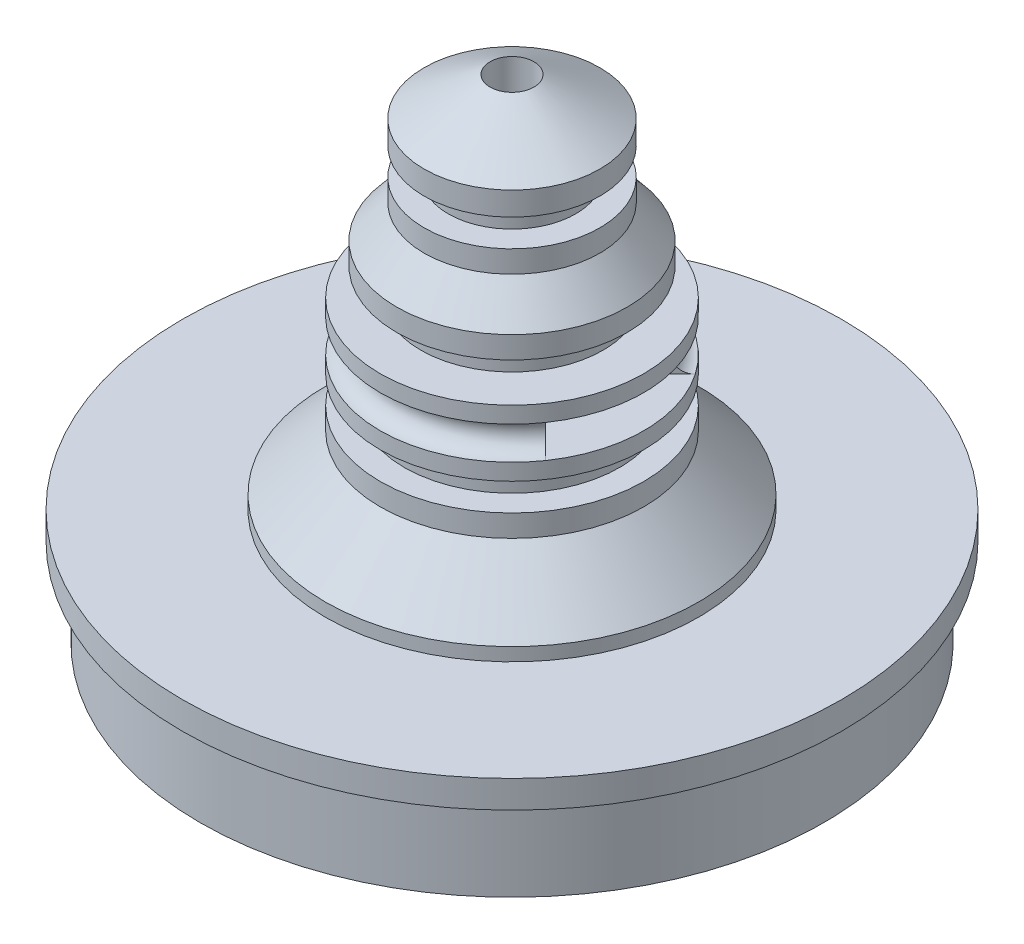
SolidWorks part; units mm, degrees
ref_plane "Спереди" through (0, 0, 0) normal (0, 0, 1) x (1, 0, 0)
ref_plane "Сверху" through (0, 0, 0) normal (0, 1, 0) x (1, 0, 0)
ref_plane "Справа" through (0, 0, 0) normal (1, 0, 0) x (0, 0, -1)
sketch "Эскиз1" plane through (0, 0, 0) normal (0, 0, 1) x (1, 0, 0)
  line L0 (0, 0) -> (0, 60) construction
  line L1 (17, 29) -> (17, 27.8)
  line L2 (2, 62.0979) -> (2, 17.3)
  line L6 (8, 56.5) -> (5.8, 56.5)
  line L7 (5.8, 56.5) -> (5.8, 54)
  line L8 (5.8, 54) -> (8, 54)
  line L10 (8, 58.6338) -> (8, 56.5)
  line L11 (8, 54) -> (8, 52)
  line L17 (12, 41.5) -> (9.0242, 41.5) construction
  line L18 (12, 44.5) -> (12, 43)
  line L19 (12, 38.5) -> (12, 40)
  line L20 (12, 36) -> (9.8, 36)
  line L21 (9.8, 36) -> (9.8, 38.5)
  line L22 (9.8, 38.5) -> (12, 38.5)
  line L23 (12, 36) -> (12, 34)
  line L24 (12, 34) -> (17, 29)
  line L29 (17, 27.8) -> (30, 27.8)
  line L33 (30, 27.8) -> (30, 25.3)
  line L34 (30, 25.3) -> (28.4, 25.3)
  line L35 (28.4, 25.3) -> (28.4, 17.3)
  line L36 (28.4, 17.3) -> (2, 17.3)
  line L37 (8, 58.6338) -> (2, 62.0979)
  line L39 (10.5, 47) -> (8.3, 47)
  line L40 (8.3, 47) -> (8.3, 44.5)
  line L41 (8.3, 44.5) -> (12, 44.5)
  line L42 (10.5, 47) -> (10.5, 49)
  line L43 (10.5, 49) -> (8, 52)
  arc A1 (12, 43) -> (12, 40) centre (12, 41.5) ccw
  point P22 (12, 43)
  dimension "D5" = 2.5
  dimension "D14" = 3
  dimension "D3" = 4
  dimension "D4" = 16
  dimension "D6" = 2
  dimension "D7" = 2.2
  dimension "D8" = 60
  dimension "D9" = 3
  dimension "D10" = 2
  dimension "D11" = 2.2
  dimension "D15" = 1.5
  dimension "D16" = 2
  dimension "D17" = 5
  dimension "D18" = 34
  dimension "D19" = 1.2
  dimension "D20" = 2.5
  dimension "D21" = 8
  dimension "D22" = 13
  dimension "D23" = 1.6
  dimension "D24" = 7.8
revolve "Повернуть1" add sketch "Эскиз1" angle 360 about L0 reverse direction yes
sketch "Эскиз3" plane through (0, 17.3, 0) normal (0, -1, 0) x (1, 0, 0)
  line L0 (50, 0) -> (-50, 0) construction
  circle A0 centre (5.9, 0) radius 2
  dimension "D1" = 4
  dimension "D2" = 5.9
ref_plane "Плоскость1" through (0, 43, 0) normal (0, -1, 0) x (-1, 0, 0)
extrude "Вырез-Вытянуть1" cut sketch "Эскиз3" against normal up to surface (25.7 mm away) up to plane "Плоскость1"
ref_plane "Плоскость2" through (0, 40, 0) normal (0, -1, 0) x (-1, 0, 0)
sketch "Эскиз4" plane through (0, 43, 0) normal (0, -1, 0) x (-1, 0, 0)
  line L0 (-4.4858, 1.4142) -> (-9.8809, 6.8094)
  line L1 (-5.9, 0) -> (-22.1819, 0) construction
  line L2 (-50, 0) -> (50, 0) construction
  line L3 (-4.4858, -1.4142) -> (-9.8809, -6.8094)
  circle A0 centre (0, 0) radius 12 construction
  arc A1 (-9.8809, 6.8094) -> (-9.8809, -6.8094) centre (0, 0) ccw
  circle A2 centre (-5.9, 0) radius 2 construction
  arc A3 (-4.4858, -1.4142) -> (-4.4858, 1.4142) centre (-5.9, 0) ccw
  dimension "D1" = 90
extrude "Вырез-Вытянуть2" cut sketch "Эскиз4" along normal up to surface (3 mm away) up to plane "Плоскость2"
